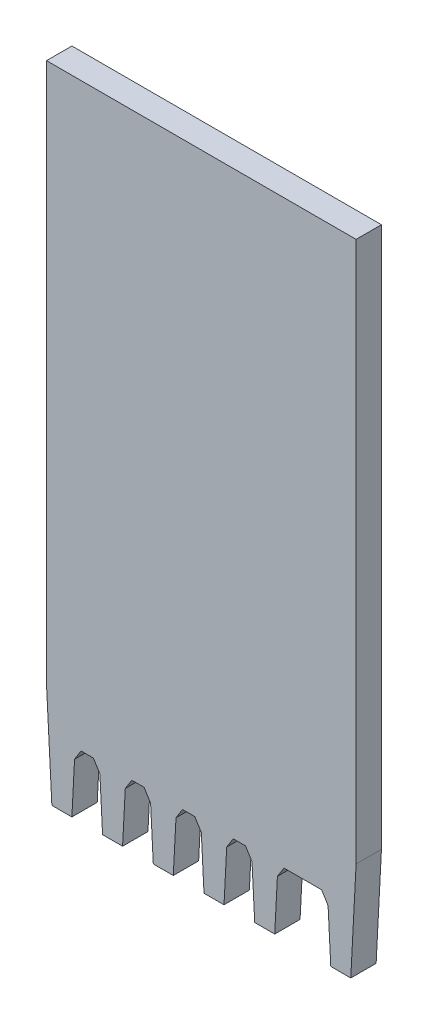
SolidWorks part; units mm, degrees
ref_plane "Front Plane" through (0, 0, 0) normal (0, 0, 1) x (1, 0, 0)
ref_plane "Top Plane" through (0, 0, 0) normal (0, 1, 0) x (1, 0, 0)
ref_plane "Right Plane" through (0, 0, 0) normal (1, 0, 0) x (0, 0, -1)
sketch "Sketch1" plane through (0, 0, 0) normal (0, 0, 1) x (1, 0, 0)
  line L0 (0, 0) -> (0, 38) construction
  line L1 (0, 38) -> (18.3124, 38) construction
  line L2 (18.3124, 38) -> (18.3124, 0) construction
  line L3 (18.3124, 0) -> (0, 0) construction
  line L4 (0, 3) -> (18.3124, 3) construction
  line L5 (0, 6) -> (18.3124, 6) construction
  line L6 (0.9062, 6) -> (0.9062, 0) construction
  line L7 (3.9062, 6) -> (3.9062, 0) construction
  line L8 (6.9062, 6) -> (6.9062, 0) construction
  line L9 (9.9062, 6) -> (9.9062, 0) construction
  line L10 (12.9062, 6) -> (12.9062, 0) construction
  line L11 (17.4062, 6) -> (17.4062, 0) construction
  line L12 (0.9062, 3) -> (3.9062, 3) construction
  line L13 (3.9062, 3) -> (6.9062, 3) construction
  line L14 (6.9062, 3) -> (9.9062, 3) construction
  line L15 (9.9062, 3) -> (12.9062, 3) construction
  line L16 (12.9062, 3) -> (17.4062, 3) construction
  line L17 (0.9062, 3) -> (0, 3) construction
  line L18 (17.4062, 3) -> (18.3124, 3) construction
  line L19 (2.4062, 3) -> (2.4062, 0) construction
  line L20 (5.4062, 3) -> (5.4062, 0) construction
  line L21 (8.4062, 3) -> (8.4062, 0) construction
  line L22 (11.4062, 3) -> (11.4062, 0) construction
  line L23 (15.1562, 3) -> (15.1562, 0) construction
  line L24 (14.4062, 3.75) -> (15.9062, 3.75) construction
  line L25 (0, 6) -> (0.3144, 0)
  line L26 (0.3144, 0) -> (1.4979, 0)
  line L27 (1.4979, 0) -> (1.6572, 3.0393)
  line L28 (3.1552, 3.0393) -> (3.3144, 0)
  line L29 (3.3144, 0) -> (4.4979, 0)
  line L30 (4.4979, 0) -> (4.6572, 3.0393)
  line L31 (6.1552, 3.0393) -> (6.3144, 0)
  line L32 (6.3144, 0) -> (7.4979, 0)
  line L33 (7.4979, 0) -> (7.6572, 3.0393)
  line L34 (9.1552, 3.0393) -> (9.3144, 0)
  line L35 (9.3144, 0) -> (10.4979, 0)
  line L36 (10.4979, 0) -> (10.6572, 3.0393)
  line L37 (12.1552, 3.0393) -> (12.3144, 0)
  line L38 (12.3144, 0) -> (13.4979, 0)
  line L39 (13.4979, 0) -> (13.6572, 3.0393)
  line L40 (16.6552, 3.0393) -> (16.8144, 0)
  line L41 (16.8144, 0) -> (17.9979, 0)
  line L42 (17.9979, 0) -> (18.3124, 6)
  line L44 (1.6572, 3.0393) -> (2.0426, 3.656)
  line L45 (0, 6) -> (0, 38)
  line L46 (0, 38) -> (18.3124, 38)
  line L47 (18.3124, 38) -> (18.3124, 6)
  line L48 (9.1562, 38) -> (9.1562, 6) construction
  line L49 (2.0426, 3.656) -> (2.7698, 3.656)
  line L50 (2.7698, 3.656) -> (3.1552, 3.0393)
  line L51 (4.6572, 3.0393) -> (5.0426, 3.656)
  line L52 (5.0426, 3.656) -> (5.7698, 3.656)
  line L53 (5.7698, 3.656) -> (6.1552, 3.0393)
  line L54 (7.6572, 3.0393) -> (8.0426, 3.656)
  line L55 (8.0426, 3.656) -> (8.7698, 3.656)
  line L56 (8.7698, 3.656) -> (9.1552, 3.0393)
  line L57 (10.6572, 3.0393) -> (11.0426, 3.656)
  line L58 (11.0426, 3.656) -> (11.7698, 3.656)
  line L59 (11.7698, 3.656) -> (12.1552, 3.0393)
  line L60 (13.6572, 3.0393) -> (14.0426, 3.656)
  line L61 (14.0426, 3.656) -> (16.2698, 3.656)
  line L62 (16.2698, 3.656) -> (16.6552, 3.0393)
  arc A0 (3.1552, 3.0393) -> (1.6572, 3.0393) centre (2.4062, 3) ccw construction
  arc A1 (6.1552, 3.0393) -> (4.6572, 3.0393) centre (5.4062, 3) ccw construction
  arc A2 (9.1552, 3.0393) -> (7.6572, 3.0393) centre (8.4062, 3) ccw construction
  arc A3 (12.1552, 3.0393) -> (10.6572, 3.0393) centre (11.4062, 3) ccw construction
  arc A4 (13.6572, 3.0393) -> (14.4062, 3.75) centre (14.4062, 3) cw construction
  arc A5 (16.6552, 3.0393) -> (15.9062, 3.75) centre (15.9062, 3) ccw construction
  dimension "D7" = 0.75
  dimension "D1" = 3
  dimension "D2" = 6
  dimension "D3" = 32
  dimension "D4" = 3
  dimension "D6" = 4.5
  dimension "D8" = 3
  dimension "D9" = 18.3124
  dimension "D10" = 38
extrude "Boss-Extrude1" add sketch "Sketch1" along normal blind 1.5
sketch "Sketch3" plane through (0, 0, 0) normal (0, 0, 1) x (1, 0, 0)
  line L0 (-0.4005, 6) -> (18.7129, 6)
  line L1 (18.7129, 3) -> (-0.4005, 3) construction
  line L2 (-0.4005, 0) -> (18.7129, 0) construction
  line L3 (-0.4005, -0.5) -> (18.7129, -0.5) construction
  line L4 (18.7129, -0.5) -> (18.7129, 6) construction
  line L5 (-0.4005, 6) -> (-0.4005, -0.5) construction
  line L6 (18.3124, 0) -> (0, 0) construction
  line L7 (0, 3) -> (18.3124, 3) construction
  line L8 (0, 6) -> (18.3124, 6) construction
  line L9 (0.3407, -0.5) -> (0, 6) construction
  line L10 (18.3124, 6) -> (17.9717, -0.5) construction
  line L11 (17.9979, 0) -> (18.3124, 6) construction
  line L12 (0, 6) -> (0.3144, 0) construction
  line L13 (5.4062, 6) -> (5.4062, -0.5) construction
  line L14 (3.9062, 6) -> (3.9062, -0.5) construction
  line L15 (5.4062, 3) -> (5.4062, 0) construction
  line L16 (3.1572, 3) -> (3.3407, -0.5) construction
  line L17 (2.7567, 3) -> (2.9401, -0.5)
  line L18 (3.1552, 3.0393) -> (3.3144, 0) construction
  line L19 (2.9401, -0.5) -> (4.8723, -0.5)
  line L20 (4.8723, -0.5) -> (5.0557, 3)
  line L21 (2.8484, 1.25) -> (3.2478, 1.2709) construction
  line L22 (5.9401, -0.5) -> (5.7567, 3)
  line L26 (7.8723, -0.5) -> (5.9401, -0.5)
  line L27 (8.0557, 3) -> (7.8723, -0.5)
  line L30 (2.4062, -0.5) -> (2.4062, 6) construction
  line L31 (2.4062, 3) -> (2.4062, 0) construction
  line L32 (8.4062, 6) -> (8.4062, -0.5) construction
  line L34 (11.4062, -0.5) -> (11.4062, 6) construction
  line L35 (15.1562, -0.5) -> (15.1562, 6) construction
  line L36 (8.4062, 3) -> (8.4062, 0) construction
  line L37 (11.4062, 3) -> (11.4062, 0) construction
  line L38 (15.1562, 3) -> (15.1562, 0) construction
  line L39 (10.8723, -0.5) -> (11.0557, 3)
  line L40 (8.9401, -0.5) -> (10.8723, -0.5)
  line L41 (8.7567, 3) -> (8.9401, -0.5)
  line L42 (11.9401, -0.5) -> (11.7567, 3)
  line L43 (13.8723, -0.5) -> (11.9401, -0.5)
  line L44 (14.0557, 3) -> (13.8723, -0.5)
  line L45 (16.4401, -0.5) -> (18.3723, -0.5)
  line L46 (16.2567, 3) -> (16.4401, -0.5)
  line L47 (18.3723, -0.5) -> (18.7129, 6)
  line L48 (1.8723, -0.5) -> (-0.0599, -0.5)
  line L49 (2.0557, 3) -> (1.8723, -0.5)
  line L50 (-0.0599, -0.5) -> (-0.4005, 6)
  line L51 (16.2567, 3) -> (14.0557, 3)
  line L52 (11.7567, 3) -> (11.0557, 3)
  line L53 (8.7567, 3) -> (8.0557, 3)
  line L54 (5.7567, 3) -> (5.0557, 3)
  line L55 (2.7567, 3) -> (2.0557, 3)
  dimension "D1" = 0.5
  dimension "D2" = 0.4
ref_plane "Plane1" through (3.9062, 0, 0) normal (1, 0, 0) x (0, 0, -1)
sketch "Sketch4" plane through (3.9062, 0, 0) normal (1, 0, 0) x (0, 0, -1)
  line L0 (0, 6) -> (0, -0.5) construction
  line L1 (0.6, 6) -> (-2.1, 6) construction
  line L2 (0.6, 6) -> (0.6, -0.5) construction
  line L3 (0.6, -0.5) -> (-2.1, -0.5) construction
  line L4 (-2.1, 6) -> (-2.1, -0.5) construction
  line L5 (-0.75, -0.5) -> (-0.75, 6) construction
  line L6 (-1.5, 6) -> (-1.5, -0.5) construction
  line L7 (0.6, 2.4005) -> (-2.1, 2.4005) construction
  line L8 (0.3, 6) -> (0.3, -0.5) construction
  line L9 (0.6, 2.4005) -> (3.846, 6) construction
  line L10 (2.2302, 6) -> (0.6, 4.1923) construction
  line L11 (0.6, 4.1923) -> (1.7139, 3.1878) construction
  line L12 (1.7139, 3.1878) -> (4.25, 6)
  line L13 (4.25, 6) -> (0.6, 6) construction
  line L14 (0.3, 1) -> (-1.8, 1) construction
  line L15 (-2.1, 0) -> (0.6, 0) construction
  line L16 (1.7139, 3.1878) -> (1.4912, 3.3887)
  line L17 (1.4912, 3.3887) -> (0.6, 2.4005)
  line L18 (-3.2139, 3.1878) -> (-5.75, 6)
  line L19 (-3.2139, 3.1878) -> (-2.9912, 3.3887)
  line L20 (-2.9912, 3.3887) -> (-2.1, 2.4005)
  line L21 (-2.1, 6) -> (-5.75, 6) construction
  line L22 (0.6, 3.0724) -> (3.2401, 6) construction
  arc A0 (0.4965, 2.2224) -> (0.6, -0.5) centre (4.2, 1) ccw
  arc A1 (0.6, 2.4005) -> (0.4965, 2.2224) centre (0.9713, 2.0656) ccw
  arc A2 (-2.1, 2.4005) -> (-1.9965, 2.2224) centre (-2.4713, 2.0656) cw
  arc A3 (-1.9965, 2.2224) -> (-2.1, -0.5) centre (-5.7, 1) cw
  dimension "D6" = 0.5
  dimension "D1" = 0.6
  dimension "D2" = 0.3
  dimension "D3" = 1.5
  dimension "D4" = 1
  dimension "D5" = 0.3
  dimension "D7" = 10
sketch "Sketch5" plane through (0, 0, 0) normal (1, 0, 0) x (0, 0, -1)
  line L0 (2.2302, 6) -> (0.6, 4.1923) construction
  line L1 (0.6, 4.1923) -> (1.7139, 3.1878) construction
  line L2 (1.7139, 3.1878) -> (4.25, 6) construction
  line L3 (2.2302, 6) -> (0.6, 4.1923) construction
  line L4 (0.6, 4.1923) -> (1.7139, 3.1878) construction
  line L5 (1.7139, 3.1878) -> (4.25, 6) construction
ref_plane "Plane2" through (0, 2.6105, -2.3541) normal (0, 0.7426, -0.6697) x (1, 0, 0)
sketch "Sketch6" plane through (0, 2.6105, -2.3541) normal (0, 0.7426, -0.6697) x (1, 0, 0)
  line L1 (3.9062, -2.362) -> (3.9062, -0.862) construction
  line L2 (3.9062, -2.362) -> (3.9062, -5.0612) construction
  line L3 (4.6562, -5.0612) -> (3.1562, -5.0612)
  line L4 (4.6562, -1.612) -> (3.1562, -1.612) construction
  line L5 (3.1562, -1.612) -> (3.1562, -5.0612)
  line L6 (4.6562, -1.612) -> (4.6562, -5.0612)
  line L10 (2.4062, -5.0612) -> (15.1562, -5.0612) construction
  line L11 (15.1562, -5.0612) -> (15.1562, -0.862) construction
  line L12 (15.1562, -0.862) -> (2.4062, -0.862) construction
  line L13 (2.4062, -0.862) -> (2.4062, -5.0612) construction
  line L14 (15.1562, 0.3349) -> (15.1562, -4.0182) construction
  line L15 (2.4062, 0.3349) -> (2.4062, -4.0182) construction
  line L16 (11.4062, -5.0612) -> (11.4062, -0.862) construction
  line L17 (8.4062, -5.0612) -> (8.4062, -0.862) construction
  line L18 (5.4062, -5.0612) -> (5.4062, -0.862) construction
  line L19 (5.4062, -4.0182) -> (5.4062, 0.3349) construction
  line L20 (8.4062, -4.0182) -> (8.4062, 0.3349) construction
  line L21 (11.4062, 0.3349) -> (11.4062, -4.0182) construction
  line L22 (0.1562, -1.612) -> (0.1562, -5.0612)
  line L23 (0.1562, -5.0612) -> (1.6562, -5.0612)
  line L24 (1.6562, -1.612) -> (1.6562, -5.0612)
  line L25 (7.6562, -1.612) -> (7.6562, -5.0612)
  line L26 (6.1562, -5.0612) -> (7.6562, -5.0612)
  line L27 (6.1562, -1.612) -> (6.1562, -5.0612)
  line L28 (10.6562, -1.612) -> (10.6562, -5.0612)
  line L29 (10.6562, -5.0612) -> (9.1562, -5.0612)
  line L30 (9.1562, -1.612) -> (9.1562, -5.0612)
  line L31 (13.6562, -1.612) -> (13.6562, -5.0612)
  line L32 (12.1562, -5.0612) -> (13.6562, -5.0612)
  line L33 (12.1562, -1.612) -> (12.1562, -5.0612)
  line L34 (18.1562, -1.612) -> (18.1562, -5.0612)
  line L35 (18.1562, -5.0612) -> (16.6562, -5.0612)
  line L36 (16.6562, -1.612) -> (16.6562, -5.0612)
  circle A0 centre (3.9062, -1.612) radius 0.75 construction
  arc A1 (4.6562, -1.612) -> (3.1562, -1.612) centre (3.9062, -1.612) ccw
  arc A2 (0.1562, -1.612) -> (1.6562, -1.612) centre (0.9062, -1.612) cw
  arc A3 (6.1562, -1.612) -> (7.6562, -1.612) centre (6.9062, -1.612) cw
  arc A4 (10.6562, -1.612) -> (9.1562, -1.612) centre (9.9062, -1.612) ccw
  arc A5 (12.1562, -1.612) -> (13.6562, -1.612) centre (12.9062, -1.612) cw
  arc A6 (18.1562, -1.612) -> (16.6562, -1.612) centre (17.4062, -1.612) ccw
ref_plane "Plane3" through (0, 1.6223, -1.463) normal (0, 0.7426, -0.6697) x (1, 0, 0)
sketch "Sketch7" plane through (0, 1.6223, -1.463) normal (0, 0.7426, -0.6697) x (1, 0, 0)
  line L0 (3.1562, -1.612) -> (3.1562, -5.0612) construction
  line L1 (4.6562, -5.0612) -> (3.1562, -5.0612) construction
  line L2 (4.6562, -1.612) -> (4.6562, -5.0612) construction
  line L3 (3.1562, -1.612) -> (3.1562, -5.0612) construction
  line L4 (4.6562, -5.0612) -> (3.1562, -5.0612) construction
  line L5 (4.6562, -1.612) -> (4.6562, -5.0612) construction
  line L6 (3.9062, -0.862) -> (3.9062, -5.0612) construction
  line L7 (4.6562, -1.612) -> (3.1562, -1.612) construction
  line L8 (4.6562, -2.362) -> (3.1562, -2.362) construction
  line L9 (3.4562, -1.612) -> (3.4562, -2.362)
  line L10 (3.4562, -2.362) -> (4.3562, -2.362)
  line L11 (4.3562, -2.362) -> (4.3562, -1.612)
  line L12 (2.4062, -0.862) -> (2.4062, -5.0612) construction
  line L13 (2.4062, -5.0612) -> (15.1562, -5.0612) construction
  line L14 (15.1562, -0.862) -> (2.4062, -0.862) construction
  line L15 (5.4062, -5.0612) -> (5.4062, -0.862) construction
  line L16 (8.4062, -5.0612) -> (8.4062, -0.862) construction
  line L17 (11.4062, -5.0612) -> (11.4062, -0.862) construction
  line L18 (15.1562, -5.0612) -> (15.1562, -0.862) construction
  line L19 (2.4062, -0.862) -> (2.4062, -5.0612) construction
  line L20 (2.4062, -5.0612) -> (15.1562, -5.0612) construction
  line L21 (15.1562, -0.862) -> (2.4062, -0.862) construction
  line L22 (5.4062, -5.0612) -> (5.4062, -0.862) construction
  line L23 (8.4062, -5.0612) -> (8.4062, -0.862) construction
  line L24 (11.4062, -5.0612) -> (11.4062, -0.862) construction
  line L25 (15.1562, -5.0612) -> (15.1562, -0.862) construction
  line L26 (0.4562, -2.362) -> (0.4562, -1.612)
  line L27 (1.3562, -2.362) -> (0.4562, -2.362)
  line L28 (1.3562, -1.612) -> (1.3562, -2.362)
  line L29 (7.3562, -2.362) -> (6.4562, -2.362)
  line L30 (7.3562, -1.612) -> (7.3562, -2.362)
  line L31 (6.4562, -2.362) -> (6.4562, -1.612)
  line L32 (9.4562, -1.612) -> (9.4562, -2.362)
  line L33 (10.3562, -2.362) -> (10.3562, -1.612)
  line L34 (9.4562, -2.362) -> (10.3562, -2.362)
  line L35 (13.3562, -1.612) -> (13.3562, -2.362)
  line L36 (12.4562, -2.362) -> (12.4562, -1.612)
  line L37 (13.3562, -2.362) -> (12.4562, -2.362)
  line L38 (16.9562, -1.612) -> (16.9562, -2.362)
  line L39 (17.8562, -2.362) -> (17.8562, -1.612)
  line L40 (16.9562, -2.362) -> (17.8562, -2.362)
  arc A0 (4.6562, -1.612) -> (3.1562, -1.612) centre (3.9062, -1.612) ccw construction
  arc A1 (4.6562, -1.612) -> (3.1562, -1.612) centre (3.9062, -1.612) ccw construction
  circle A2 centre (3.9062, -1.612) radius 0.45 construction
  arc A3 (4.3562, -1.612) -> (3.4562, -1.612) centre (3.9062, -1.612) ccw
  arc A4 (0.4562, -1.612) -> (1.3562, -1.612) centre (0.9062, -1.612) cw
  arc A5 (6.4562, -1.612) -> (7.3562, -1.612) centre (6.9062, -1.612) cw
  arc A6 (10.3562, -1.612) -> (9.4562, -1.612) centre (9.9062, -1.612) ccw
  arc A7 (12.4562, -1.612) -> (13.3562, -1.612) centre (12.9062, -1.612) cw
  arc A8 (17.8562, -1.612) -> (16.9562, -1.612) centre (17.4062, -1.612) ccw
ref_plane "bisect" through (0, 0, 0.75) normal (0, 0, 1) x (1, 0, 0)
ref_plane "insert_surface" through (0, 6, 0) normal (0, 1, 0) x (1, 0, 0)
sketch "Sketch8" plane through (0, 6, 0) normal (0, 1, 0) x (1, 0, 0)
  line L0 (18.7129, -0.75) -> (-0.4005, -0.75) construction
  line L1 (-0.4005, 0.6) -> (18.7129, 0.6)
  line L2 (-0.4005, 0.6) -> (-0.4005, -2.1)
  line L3 (-0.4005, -2.1) -> (18.7129, -2.1)
  line L4 (18.7129, 0.6) -> (18.7129, -2.1)
  line L5 (9.1562, 0.6) -> (9.1562, -2.1) construction
  line L6 (0, 0) -> (18.3124, 0) construction
  line L7 (0, 0) -> (0, -1.5) construction
  line L8 (0, -1.5) -> (18.3124, -1.5) construction
  line L9 (18.3124, 0) -> (18.3124, -1.5) construction
  line L10 (18.7129, 0.3) -> (-0.4005, 0.3) construction
  line L11 (18.7129, -1.8) -> (-0.4005, -1.8) construction
sketch "Sketch9" plane through (0, 0, 0) normal (0, 0, 1) x (1, 0, 0)
  line L0 (18.3723, -0.5) -> (18.7129, 6) construction
  line L1 (-0.4005, 6) -> (18.7129, 6) construction
  line L2 (-0.0599, -0.5) -> (-0.4005, 6) construction
  line L3 (1.8723, -0.5) -> (-0.0599, -0.5) construction
  line L4 (2.0557, 3) -> (1.8723, -0.5) construction
  line L5 (2.7567, 3) -> (2.0557, 3) construction
  line L6 (2.7567, 3) -> (2.9401, -0.5) construction
  line L7 (2.9401, -0.5) -> (4.8723, -0.5) construction
  line L8 (4.8723, -0.5) -> (5.0557, 3) construction
  line L9 (5.7567, 3) -> (5.0557, 3) construction
  line L10 (5.9401, -0.5) -> (5.7567, 3) construction
  line L11 (7.8723, -0.5) -> (5.9401, -0.5) construction
  line L12 (8.0557, 3) -> (7.8723, -0.5) construction
  line L13 (8.7567, 3) -> (8.0557, 3) construction
  line L14 (8.7567, 3) -> (8.9401, -0.5) construction
  line L15 (8.9401, -0.5) -> (10.8723, -0.5) construction
  line L16 (10.8723, -0.5) -> (11.0557, 3) construction
  line L17 (11.7567, 3) -> (11.0557, 3) construction
  line L18 (11.9401, -0.5) -> (11.7567, 3) construction
  line L19 (13.8723, -0.5) -> (11.9401, -0.5) construction
  line L20 (14.0557, 3) -> (13.8723, -0.5) construction
  line L21 (16.2567, 3) -> (14.0557, 3) construction
  line L22 (16.2567, 3) -> (16.4401, -0.5) construction
  line L23 (16.4401, -0.5) -> (18.3723, -0.5) construction
  line L24 (18.3723, -0.5) -> (18.7129, 6)
  line L25 (-0.4005, 6) -> (18.7129, 6) construction
  line L26 (-0.0599, -0.5) -> (-0.4005, 6)
  line L27 (1.8723, -0.5) -> (-0.0599, -0.5)
  line L28 (2.0557, 3) -> (1.8723, -0.5)
  line L29 (2.7567, 3) -> (2.0557, 3) construction
  line L30 (2.7567, 3) -> (2.9401, -0.5)
  line L31 (2.9401, -0.5) -> (4.8723, -0.5)
  line L32 (4.8723, -0.5) -> (5.0557, 3)
  line L33 (5.7567, 3) -> (5.0557, 3) construction
  line L34 (5.9401, -0.5) -> (5.7567, 3)
  line L35 (7.8723, -0.5) -> (5.9401, -0.5)
  line L36 (8.0557, 3) -> (7.8723, -0.5)
  line L37 (8.7567, 3) -> (8.0557, 3) construction
  line L38 (8.7567, 3) -> (8.9401, -0.5)
  line L39 (8.9401, -0.5) -> (10.8723, -0.5)
  line L40 (10.8723, -0.5) -> (11.0557, 3)
  line L41 (11.7567, 3) -> (11.0557, 3) construction
  line L42 (11.9401, -0.5) -> (11.7567, 3)
  line L43 (13.8723, -0.5) -> (11.9401, -0.5)
  line L44 (14.0557, 3) -> (13.8723, -0.5)
  line L45 (16.2567, 3) -> (14.0557, 3) construction
  line L46 (16.2567, 3) -> (16.4401, -0.5)
  line L47 (16.4401, -0.5) -> (18.3723, -0.5)
  line L48 (16.2567, 3) -> (16.2567, 6)
  line L49 (14.0557, 3) -> (14.0557, 6)
  line L50 (11.7567, 3) -> (11.7567, 6)
  line L51 (18.7129, 6) -> (-0.4005, 6) construction
  line L52 (11.0557, 3) -> (11.0557, 6)
  line L53 (-0.4005, 6) -> (18.7129, 6) construction
  line L54 (8.7567, 3) -> (8.7567, 6)
  line L55 (8.0557, 3) -> (8.0557, 6)
  line L58 (5.7567, 3) -> (5.7567, 6)
  line L60 (5.0557, 3) -> (5.0557, 6)
  line L62 (15.1562, -0.5) -> (15.1562, 6) construction
  line L63 (15.1562, -0.5) -> (15.1562, 6) construction
  line L64 (2.7567, 3) -> (2.7567, 6)
  line L65 (2.0557, 3) -> (2.0557, 6)
  line L67 (18.7129, 6) -> (16.2567, 6)
  line L68 (14.0557, 6) -> (11.7567, 6)
  line L69 (11.0557, 6) -> (8.7567, 6)
  line L70 (8.0557, 6) -> (5.7567, 6)
  line L71 (5.0557, 6) -> (2.7567, 6)
  line L72 (2.0557, 6) -> (-0.4005, 6)
